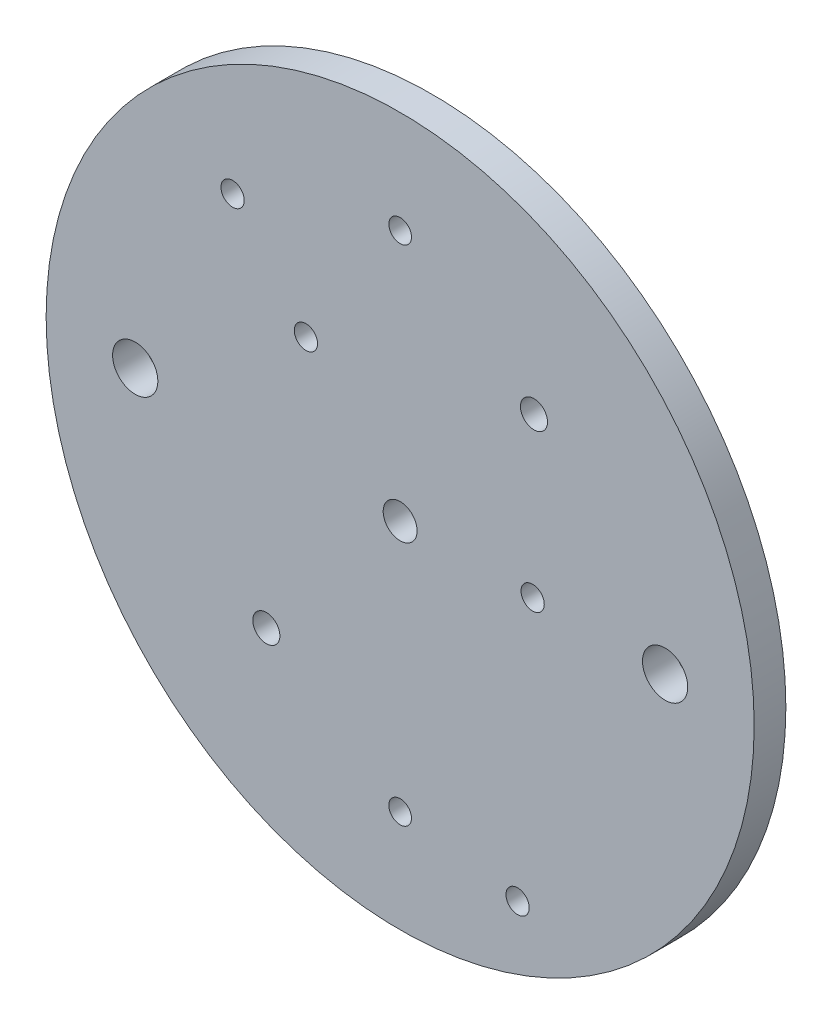
SolidWorks part; units mm, degrees
material "E-Glass Fiber"
ref_plane "Front Plane" through (0, 0, 0) normal (0, 0, 1) x (1, 0, 0)
ref_plane "Top Plane" through (0, 0, 0) normal (0, 1, 0) x (1, 0, 0)
ref_plane "Right Plane" through (0, 0, 0) normal (1, 0, 0) x (0, 0, -1)
sketch "Sketch1" plane through (0, 0, 0) normal (0, 0, 1) x (1, 0, 0)
  circle A0 centre (0, 0) radius 49.6697
  dimension "D1" = 99.3394
extrude "Boss-Extrude1" add sketch "Sketch1" along normal blind 4.445
sketch "Sketch2" plane through (0, 0, 4.445) normal (0, 0, 1) x (1, 0, 0)
  line L0 (37.1729, 0) -> (0, 0) construction
  line L1 (0, 0) -> (-37.1729, 0) construction
  line L2 (0, 0) -> (0, 35.306) construction
  line L3 (0, 0) -> (18.7758, 22.3762) construction
  line L4 (0, 0) -> (-18.3677, 21.8897) construction
  line L5 (16.4781, -37.9415) -> (18.5865, 0) construction
  line L6 (-18.3677, 21.8897) -> (-23.5106, 28.0188) construction
  line L7 (-18.3677, 21.8897) -> (-13.2247, 15.7606) construction
  circle A0 centre (0, 0) radius 2.3812
  circle A1 centre (37.1729, 0) radius 3.175
  circle A2 centre (-37.1729, 0) radius 3.175
  dimension "D1" = 4.7625
  dimension "D2" = 6.35
  dimension "D3" = 74.3458
  dimension "D5" = 29.21
  dimension "D6" = 50
  dimension "D4" = 35.306
  dimension "D7" = 28.575
  dimension "D8" = 50
  dimension "D9" = 38
  dimension "D10" = 16.002
extrude "Cut-Extrude1" cut sketch "Sketch2" against normal through all
hole_wizard "#4 Clearance Hole1" positions "Sketch4" profile "Sketch3" hole size "#4" standard "ANSI Inch" end condition through all
sketch "Sketch4" plane through (0, 0, 4.445) normal (0, 0, 1) x (1, 0, 0)
  point P4 (18.5865, 0)
  point P7 (16.4781, -37.9415)
  point P10 (-23.5106, 28.0188)
  point P13 (-13.2247, 15.7606)
sketch "Sketch3" plane through (18.5865, 0, 4.445) normal (1, 0, 0) x (0, -1, 0)
  line L0 (0, 0) -> (0, 4.445)
  line L1 (0, 4.445) -> (1.6319, 4.445)
  line L2 (1.6319, 4.445) -> (1.6319, 0)
  line L5 (1.6319, 0) -> (0, 0)
  line L11 (0, -6.35) -> (0, 107.95) construction
  dimension "Thru Hole Dia." = 3.2639
  dimension "Thru Hole Depth" = 4.445
hole_wizard "#6 Clearance Hole1" positions "Sketch6" profile "Sketch7" hole size "#6" standard "ANSI Inch" end condition through all
sketch "Sketch6" plane through (0, 0, 4.445) normal (0, 0, 1) x (1, 0, 0)
  point P0 (18.7758, 22.3762)
sketch "Sketch7" plane through (18.7758, 22.3762, 4.445) normal (1, 0, 0) x (0, -1, 0)
  line L0 (0, 0) -> (0, 4.445)
  line L1 (0, 4.445) -> (1.8986, 4.445)
  line L2 (1.8986, 4.445) -> (1.8986, 0)
  line L5 (1.8986, 0) -> (0, 0)
  line L11 (0, -6.35) -> (0, 107.95) construction
  dimension "Thru Hole Dia." = 3.7973
  dimension "Thru Hole Depth" = 4.445
hole_wizard "1/8 (0.125) Diameter Hole1" positions "Sketch9" profile "Sketch10" hole size "1/8" standard "ANSI Inch" end condition through all
sketch "Sketch9" plane through (0, 0, 4.445) normal (0, 0, 1) x (1, 0, 0)
  point P0 (0, 35.306)
sketch "Sketch10" plane through (0, 35.306, 4.445) normal (1, 0, 0) x (0, -1, 0)
  line L0 (0, 0) -> (0, 4.445)
  line L1 (0, 4.445) -> (1.5875, 4.445)
  line L2 (1.5875, 4.445) -> (1.5875, 0)
  line L5 (1.5875, 0) -> (0, 0)
  line L11 (0, -6.35) -> (0, 107.95) construction
  dimension "Thru Hole Dia." = 3.175
  dimension "Thru Hole Depth" = 4.445
pattern_circular "CirPattern1" count 2 over 180 about axis through (0, 0, 0) along (0, 0, 1) of "#6 Clearance Hole1", "1/8 (0.125) Diameter Hole1"
